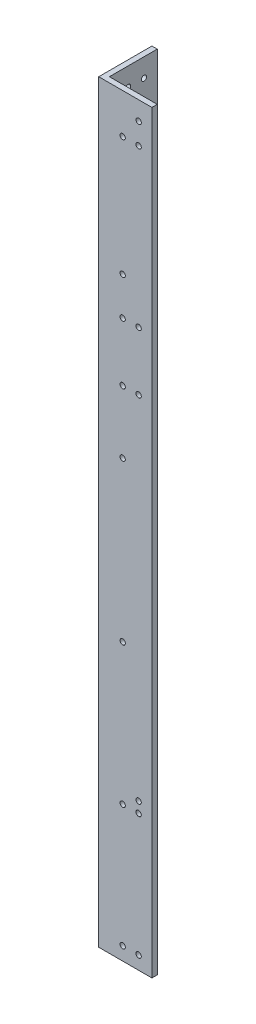
SolidWorks part; units mm, degrees
ref_plane "Front Plane" through (0, 0, 0) normal (0, 0, 1) x (1, 0, 0)
ref_plane "Top Plane" through (0, 0, 0) normal (0, 1, 0) x (1, 0, 0)
ref_plane "Right Plane" through (0, 0, 0) normal (1, 0, 0) x (0, 0, -1)
sketch "Sketch2" plane through (0, 0, 0) normal (0, 1, 0) x (1, 0, 0)
  line L0 (0, 31.75) -> (3.175, 31.75)
  line L1 (3.175, 31.75) -> (3.175, 3.175)
  line L2 (3.175, 3.175) -> (31.75, 3.175)
  line L3 (31.75, 3.175) -> (31.75, 0)
  line L4 (31.75, 0) -> (0, 0)
  line L5 (0, 0) -> (0, 31.75)
  point P9 (1.5875, 31.75)
  point P10 (31.75, 1.5875)
  dimension "D4" = 3.175
  dimension "D1" = 31.75
  dimension "D2" = 31.75
  dimension "D3" = 3.175
extrude "Boss-Extrude1" add sketch "Sketch2" along normal blind 450
sketch "LeftSideHoles-Sketch3" plane through (0, 0, 0) normal (0, 0, 1) x (1, 0, 0)
  line L0 (0, 0) -> (31.75, 0) construction
  line L1 (0, 450) -> (31.75, 450) construction
  line L3 (0, 450) -> (0, 0) construction
  circle A0 centre (14.2875, 81.1125) radius 1.5875
  circle A1 centre (23.8125, 81.1125) radius 1.5875
  circle A3 centre (23.8125, 87.4625) radius 1.5875
  circle A5 centre (14.2875, 426.1875) radius 1.5875
  circle A6 centre (23.8125, 438.8875) radius 1.5875
  circle A7 centre (23.8125, 426.1875) radius 1.5875
  circle A10 centre (14.2875, 332.3776) radius 1.5875
  circle A11 centre (23.8125, 332.3776) radius 1.5875
  circle A12 centre (14.2875, 297.4526) radius 1.5875
  circle A13 centre (23.8125, 297.4526) radius 1.5875
  circle A14 centre (14.2875, 7.9375) radius 1.5875
  circle A15 centre (23.8125, 7.9375) radius 1.5875
  circle A16 centre (14.2875, 165) radius 1.5875
  circle A17 centre (14.2875, 260) radius 1.5875
  circle A18 centre (14.2875, 355) radius 1.5875
  point P24 (15.875, 0)
  dimension "D4" = 3.175
  dimension "D1" = 81.1125
  dimension "D2" = 14.2875
  dimension "D10" = 7.9375
  dimension "D7" = 34.925
  dimension "D3" = 9.525
  dimension "D11" = 332.3776
  dimension "D12" = 165
  dimension "D13" = 95
  dimension "D5" = 6.35
  dimension "D6" = 12.7
  dimension "D8" = 11.1125
  dimension "D9" = 95
sketch "BackSideHoles-Sketch4" plane through (0, 0, 0) normal (-1, 0, 0) x (0, 0, 1)
  line L0 (-31.75, 450) -> (0, 450) construction
  line L2 (0, 450) -> (0, 0) construction
  line L3 (-31.75, 0) -> (0, 0) construction
  circle A0 centre (-23.8125, 81.1125) radius 1.5875
  circle A2 centre (-23.8125, 87.4625) radius 1.5875
  circle A3 centre (-14.2875, 87.4625) radius 1.5875
  circle A4 centre (-23.8125, 438.8875) radius 1.5875
  circle A5 centre (-14.2875, 438.8875) radius 1.5875
  circle A6 centre (-23.8125, 426.1875) radius 1.5875
  circle A10 centre (-23.8125, 330.7776) radius 1.5875
  circle A11 centre (-14.2875, 330.7776) radius 1.5875
  circle A12 centre (-23.8125, 324.4276) radius 1.5875
  circle A13 centre (-14.2875, 324.4276) radius 1.5875
  circle A14 centre (-14.2875, 165) radius 1.5875
  circle A15 centre (-14.2875, 260) radius 1.5875
  circle A17 centre (-23.8125, 7.9375) radius 1.5875
  circle A18 centre (-14.2875, 7.9375) radius 1.5875
  circle A19 centre (-14.2875, 355) radius 1.5875
  dimension "D4" = 3.175
  dimension "D2" = 14.2875
  dimension "D5" = 6.35
  dimension "D6" = 11.1125
  dimension "D8" = 6.35
  dimension "D7" = 12.7
  dimension "D1" = 330.7776
  dimension "D10" = 165
  dimension "D11" = 95
  dimension "D13" = 7.9375
  dimension "D3" = 81.1125
  dimension "D9" = 9.525
  dimension "D12" = 95
extrude "LeftSideHoles-Cut-Extrude1" cut sketch "LeftSideHoles-Sketch3" against normal blind 3.175
extrude "BackSideHoles-Cut-Extrude2" cut sketch "BackSideHoles-Sketch4" against normal blind 3.175
equation "\"RailThickness\"= .125in'Spec"
equation "\"VSWidth\"= 1.25in'Spec"
equation "\"VSHeight\"= 1.25in'Spec"
equation "\"VSLength\"= 450mm"
equation "\"HoleOffsetFromEdge\"= \"RailThickness\" * 2.5"
equation "\"HoleOffsetFromSide\"= \"RailThickness\" * 3.5"
equation "\"LegHeight\"= 70mm'Space needed for PSU/Stepper/Electronics"
equation "\"VSBottomSideRailHoleY1FromBottomOfLowerRail\"= \"V1 BottomOfLowerRail\" + \"HoleOffsetFromSide\"'Equals 81.1125"
equation "\"VSSideRailHoleX1FromSide\"= \"HoleOffsetFromSide\" + \"RailThickness\""
equation "\"FasteningHoleDiameter\"= .125in"
equation "\"VSBottomSideRailHoleY2FromY1\"= \"LowerRailHeight\" - \"HoleOffsetFromSide\" - \"HoleOffsetFromEdge\"'Equals 6.35"
equation "\"VSTopSideRailHoleY1FromEdge\"= \"HoleOffsetFromEdge\" + \"RailThickness\""
equation "\"D4@LeftSideHoles-Sketch3\"=\"FasteningHoleDiameter\""
equation "\"D1@LeftSideHoles-Sketch3\"=\"VSBottomSideRailHoleY1FromBottomOfLowerRail\""
equation "\"D2@LeftSideHoles-Sketch3\"=\"VSSideRailHoleX1FromSide\""
equation "\"D1@Boss-Extrude1\"=\"VSLength\""
equation "\"D4@BackSideHoles-Sketch4\" = \"FasteningHoleDiameter\""
equation "\"VSMidSideRailHoleY1FromV8TopOfMidSideRail\"= \"V8 ToTopOfMidSideRail\" - \"HoleOffsetFromEdge\"'Equals 332.37764"
equation "\"LowerRailHeight\"= 1.00in"
equation "\"D1@Sketch2\"=\"VSHeight\""
equation "\"D2@Sketch2\"=\"VSWidth\""
equation "\"MidBackRailHeight\"= 1.00in"
equation "\"VSMidBackRailHoleY1FromV7TopOfMidBackRail\"= \"V7 ToTopOfMidBackRail\" - \"HoleOffsetFromEdge\"'Equals 330.77764"
equation "\"TopRailHeight\"= 1.25in"
equation "\"MidLeftOrRightSideRailHeight\"= 2.0in"
equation "\"D10@LeftSideHoles-Sketch3\"=\"HoleOffsetFromEdge\""
equation "\"VSMidBackRailHoleY2FromY1\"= \"MidBackRailHeight\" - \"HoleOffsetFromSide\" - \"HoleOffsetFromEdge\"'Equals 6.35"
equation "\"VSMidSideRailHoleY2FromY1\"= \"MidLeftOrRightSideRailHeight\" - \"HoleOffsetFromEdge\" * 2'Equals 34.925"
equation "\"D7@LeftSideHoles-Sketch3\"=\"VSMidSideRailHoleY2FromY1\""
equation "\"D8@BackSideHoles-Sketch4\"=\"VSMidBackRailHoleY2FromY1\""
equation "\"D6@BackSideHoles-Sketch4\"=\"VSTopSideRailHoleY1FromEdge\""
equation "\"VSTopSideRailHoleY2FromY1\"= \"TopRailHeight\" - \"VSTopSideRailHoleY1FromEdge\" - \"HoleOffsetFromEdge\"'Equals 12.7"
equation "\"D7@BackSideHoles-Sketch4\"=\"VSTopSideRailHoleY2FromY1\""
equation "\"VSBottomSideRailHoleX2FromX1\"= \"VSWidth\" - \"VSSideRailHoleX1FromSide\" - \"HoleOffsetFromEdge\""
equation "\"D3@LeftSideHoles-Sketch3\"=\"VSBottomSideRailHoleX2FromX1\""
equation "\"V1 BottomOfLowerRail\"= \"LegHeight\""
equation "\"StepperShaftLength\"= 24mm'Pulley will be attached to the end"
equation "\"ZAxisLeadScrewLength\"= 200mm"
equation "\"LM8UUHeight\"= 24mm'Spec"
equation "\"V2 ToBedAtTopOfZAxis\"= \"V1 BottomOfLowerRail\" - \"LowerEnclosureThickness\" + \"StepperShaftLength\" + \"ZAxisLeadScrewLength\" - \"LM8UUHeight\" / 2"
equation "\"HotEndToTopOfXAxisGB\"= 63.315144mm'Measured from the100.Should be 63.315144"
equation "\"TopOfGBToBottomOfLinearRail\"= \"LinearGBWidth\" / 2 + \"LinearRailWidth\" / 2"
equation "\"LinearGBWidth\"= 27mm'Spec"
equation "\"V5 ToBottomOfXAxisLinearRail\"= \"V4 ToTopOfBuildPlate/HotEndTip\" + \"HotEndToTopOfXAxisGB\" - \"TopOfGBToBottomOfLinearRail\""
equation "\"LinearRailWidth\"= 12mm'Spec"
equation "\"GABUpperHeight\"= 6mm"
equation "\"GABMidWallHeight\"= 28mm'Must equal 28 or changes alignment"
equation "\"V7 ToBottomOfMidBackRail\"= \"V6 ToMiddleOfYAxisGantryBlock\" - \"StepperShaftLength\" / 2"
equation "\"D1@BackSideHoles-Sketch4\" = \"VSMidBackRailHoleY1FromV7TopOfMidBackRail\""
equation "\"D11@LeftSideHoles-Sketch3\"=\"VSMidSideRailHoleY1FromV8TopOfMidSideRail\""
equation "\"V4 ToTopOfBuildPlate/HotEndTip\"= \"V2 ToBedAtTopOfZAxis\" + \"BedToBuildPlateStandoffLength\" + \"BuildPlateHeight\""
equation "\"BedToBuildPlateStandoffLength\"= 15mm"
equation "\"BuildPlateHeight\"= 8mm'Spec"
equation "\"V8 ToTopOfMidSideRail\" = \"V6 ToMiddleOfYAxisGantryBlock\" + \"MidSideRailVerticalOffset\""
equation "\"VSEnclosureOffsets\"= ( \"VSLength\" - \"LegHeight\" ) / 4"
equation "\"D12@LeftSideHoles-Sketch3\"=\"LegHeight\" + \"VSEnclosureOffsets\""
equation "\"D13@LeftSideHoles-Sketch3\"=\"VSEnclosureOffsets\""
equation "\"D10@BackSideHoles-Sketch4\"=\"LegHeight\" + \"VSEnclosureOffsets\""
equation "\"D11@BackSideHoles-Sketch4\"=\"VSEnclosureOffsets\""
equation "\"D13@BackSideHoles-Sketch4\"=\"HoleOffsetFromEdge\""
equation "\"D5@BackSideHoles-Sketch4\"=\"VSBottomSideRailHoleY2FromY1\""
equation "\"D3@BackSideHoles-Sketch4\"=\"VSBottomSideRailHoleY1FromBottomOfLowerRail\""
equation "\"D2@BackSideHoles-Sketch4\"=\"VSSideRailHoleX1FromSide\""
equation "\"D5@LeftSideHoles-Sketch3\"=\"VSBottomSideRailHoleY2FromY1\""
equation "\"D6@LeftSideHoles-Sketch3\"=\"VSTopSideRailHoleY2FromY1\""
equation "\"D8@LeftSideHoles-Sketch3\"=\"VSTopSideRailHoleY1FromEdge\""
equation "\"LowerEnclosureThickness\"= 5mm"
equation "\"V7 ToTopOfMidBackRail\"= \"V7 ToBottomOfMidBackRail\" + \"MidBackRailHeight\""
equation "\"GABHeight\"= \"GABLowerHeight\" + \"GABMidWallHeight\" + \"GABUpperHeight\""
equation "\"GABLowerHeight\"= 3mm"
equation "\"V6 ToMiddleOfYAxisGantryBlock\"= \"V5 ToBottomOfXAxisLinearRail\" - \"GABHeight\" / 2'Equals 325.31514"
equation "\"D9@LeftSideHoles-Sketch3\"=\"VSEnclosureOffsets\""
equation "\"D12@BackSideHoles-Sketch4\"=\"VSEnclosureOffsets\""
equation "\"MidSideRailVerticalOffset\"= \"LinearRailWidth\" + 3mm'Allows space for RodStabilizer to attach to bottom of MidSideRail"
